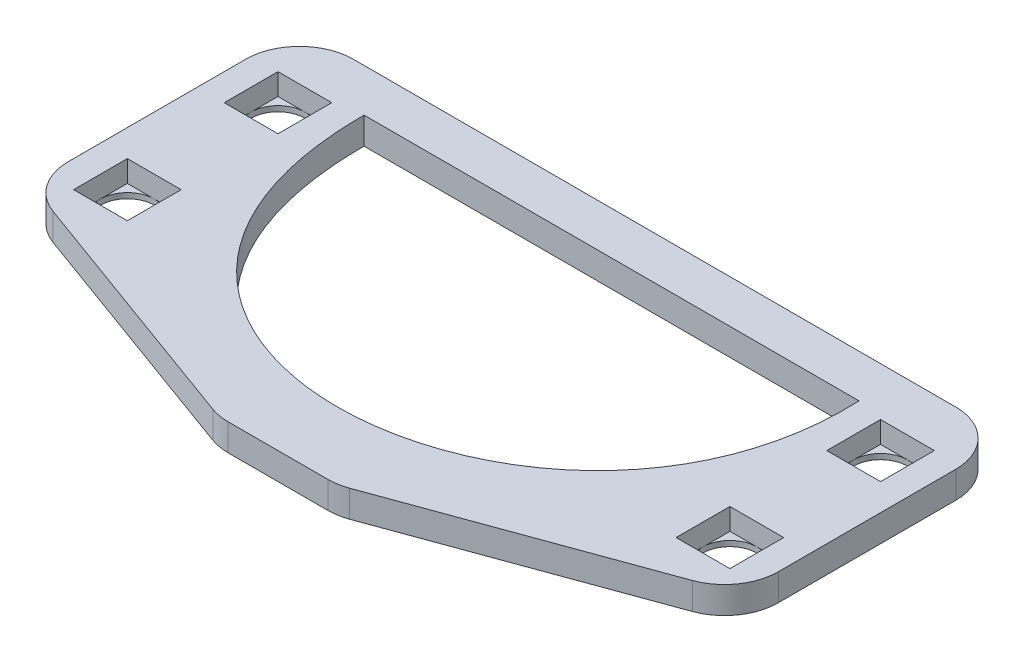
SolidWorks part; units mm, degrees
ref_plane "Front Plane" through (0, 0, 0) normal (0, 0, 1) x (1, 0, 0)
ref_plane "Top Plane" through (0, 0, 0) normal (0, 1, 0) x (1, 0, 0)
ref_plane "Right Plane" through (0, 0, 0) normal (1, 0, 0) x (0, 0, -1)
sketch "Sketch1" plane through (0, 0, 0) normal (0, 1, 0) x (1, 0, 0)
  line L1 (0, 0) -> (66, 0)
  line L2 (0, 0) -> (0, 35)
  line L3 (0, 35) -> (66, 35)
  line L4 (66, 0) -> (66, 35)
  dimension "D1" = 66
  dimension "D2" = 35
extrude "Boss-Extrude1" add sketch "Sketch1" along normal blind 2.5
sketch "Sketch2" plane through (0, 2.5, 0) normal (0, 1, 0) x (1, 0, 0)
  line L0 (10, 31) -> (56, 31)
  line L1 (0, 35) -> (0, 0) construction
  line L2 (66, 35) -> (0, 35) construction
  line L3 (66, 0) -> (66, 35) construction
  line L5 (7.5, 30.5) -> (2.5, 30.5)
  line L6 (7.5, 30.5) -> (7.5, 25.5)
  line L7 (7.5, 25.5) -> (2.5, 25.5)
  line L8 (2.5, 30.5) -> (2.5, 25.5)
  line L9 (7.5, 30.5) -> (2.5, 25.5) construction
  line L10 (7.5, 25.5) -> (2.5, 30.5) construction
  line L11 (7.5, 16.5) -> (2.5, 16.5)
  line L12 (7.5, 16.5) -> (7.5, 11.5)
  line L13 (7.5, 11.5) -> (2.5, 11.5)
  line L14 (2.5, 16.5) -> (2.5, 11.5)
  line L15 (7.5, 16.5) -> (2.5, 11.5) construction
  line L16 (7.5, 11.5) -> (2.5, 16.5) construction
  line L17 (58.5, 16.5) -> (63.5, 16.5)
  line L18 (58.5, 16.5) -> (58.5, 11.5)
  line L19 (58.5, 11.5) -> (63.5, 11.5)
  line L20 (63.5, 16.5) -> (63.5, 11.5)
  line L21 (58.5, 16.5) -> (63.5, 11.5) construction
  line L22 (58.5, 11.5) -> (63.5, 16.5) construction
  line L23 (58.5, 30.5) -> (63.5, 30.5)
  line L24 (58.5, 30.5) -> (58.5, 25.5)
  line L25 (58.5, 25.5) -> (63.5, 25.5)
  line L26 (63.5, 30.5) -> (63.5, 25.5)
  line L27 (58.5, 30.5) -> (63.5, 25.5) construction
  line L28 (58.5, 25.5) -> (63.5, 30.5) construction
  circle A0 centre (5, 28) radius 2.5
  circle A1 centre (5, 14) radius 2.5
  circle A2 centre (61, 28) radius 2.5
  circle A3 centre (61, 14) radius 2.5
  spline S0 degree 3 poles (56, 31) (57.2919, 0.36) (9.9562, -4.2257) (10, 31) knots 0 0 0 0 1 1 1 1
  dimension "D3" = 4
  dimension "D5" = 5
  dimension "D6" = 5
  dimension "D7" = 5
  dimension "D8" = 5
  dimension "D1" = 46
  dimension "D2" = 10
  dimension "D4" = 14
  dimension "D9" = 5
  dimension "D10" = 5
  dimension "D11" = 7
  dimension "D12" = 5
  dimension "D13" = 5
  dimension "D14" = 5
  dimension "D15" = 5
  dimension "D16" = 5
  dimension "D17" = 5
  dimension "D18" = 5
  dimension "D19" = 5
extrude "Cut-Extrude1" cut sketch "Sketch2" against normal through all contours A0 | A0 | A1 | A3 | A2 | S0 L0 region at (5, 2.5, -28)
extrude "Cut-Extrude2" cut sketch "Sketch2<3>" against normal blind 2 contours A1 L13 L12 | A1 L12 L11 | A1 L11 L14 | A1 L14 L13 | A0 L5 L8 | A0 L6 L5 | A0 L7 L6 | A0 L8 L7 | A2 L23 L24 | A2 L26 L23 | A2 L25 L26 | A2 L24 L25 | A3 L19 L20 | A3 L18 L19 | A3 L17 L18 | A3 L20 L17 region at (6.9416, 2.5, -29.9416) region at (3.0584, 2.5, -29.9416) region at (6.9416, 2.5, -26.0584) region at (3.0584, 2.5, -26.0584) region at (6.9416, 2.5, -15.9416) region at (3.0584, 2.5, -15.9416) region at (6.9416, 2.5, -12.0584) region at (3.0584, 2.5, -12.0584) region at (59.0584, 2.5, -15.9416) region at (62.9416, 2.5, -15.9416) region at (59.0584, 2.5, -12.0584) region at (62.9416, 2.5, -12.0584) region at (59.0584, 2.5, -29.9416) region at (62.9416, 2.5, -29.9416) region at (59.0584, 2.5, -26.0584) region at (62.9416, 2.5, -26.0584)
sketch "Sketch2<3>" plane through (0, 2.5, 0) normal (0, 1, 0) x (1, 0, 0) same geometry as "Sketch2"
chamfer "Chamfer1" distance 10 angle 70 2 edges at (66, 1.25, 0) (0, 1.25, 0) first distance on face at (66, 1.25, -17.5) first distance on face at (0, 1.25, -17.5)
fillet "Fillet1" radius 5 6 edges at (27.4748, 1.25, 0) (38.5252, 1.25, 0) (66, 1.25, -10) (66, 1.25, -35) (0, 1.25, -35) (0, 1.25, -10)
